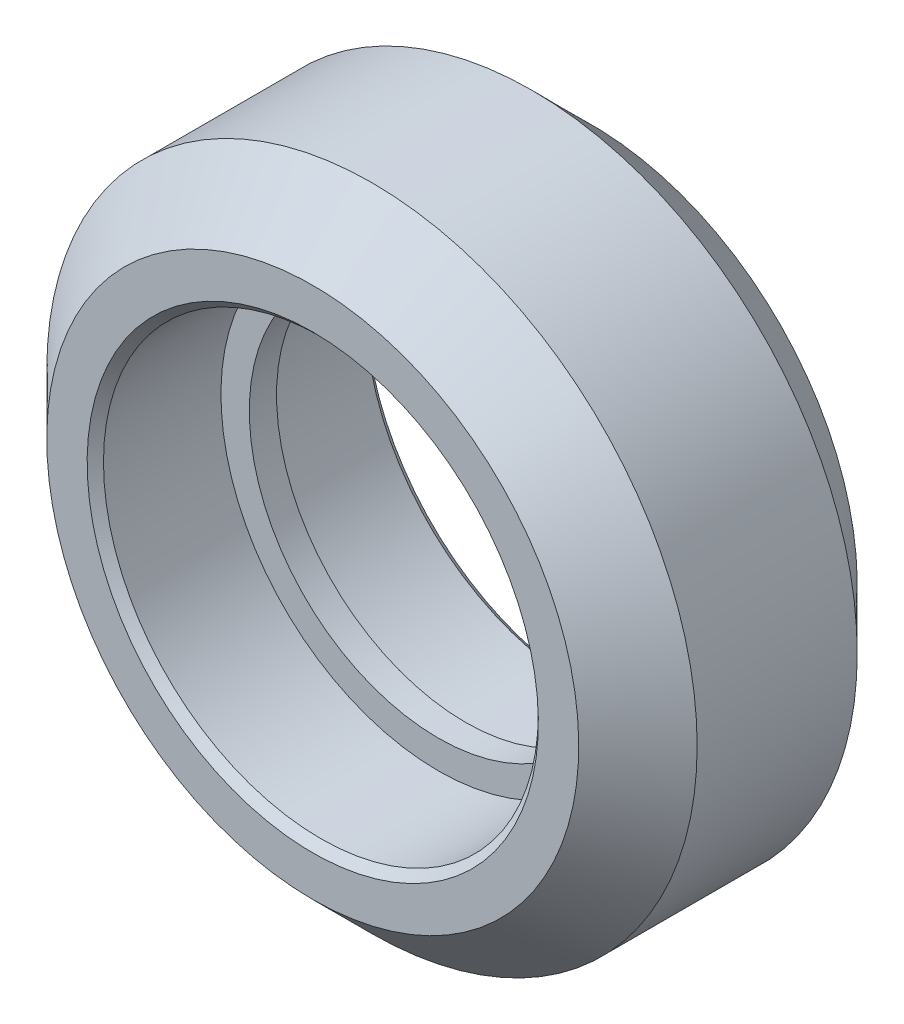
SolidWorks part; units mm, degrees
ref_plane "Front Plane" through (0, 0, 0) normal (0, 0, 1) x (1, 0, 0)
ref_plane "Top Plane" through (0, 0, 0) normal (0, 1, 0) x (1, 0, 0)
ref_plane "Right Plane" through (0, 0, 0) normal (1, 0, 0) x (0, 0, -1)
sketch "Sketch1" plane through (0, 0, 0) normal (1, 0, 0) x (0, 0, -1)
  line L0 (-5.115, 0) -> (5.115, 0) construction
  line L1 (-5.115, 11.945) -> (5.115, 11.945) construction
  line L2 (0, 11.945) -> (0, 0) construction
  line L3 (-5.115, 7.987) -> (5.115, 7.987) construction
  line L4 (-5.115, 9.77) -> (5.115, 9.77) construction
  line L5 (0, 11.945) -> (0, 15.716) construction
  line L6 (-0.5, 6.945) -> (0.5, 6.945) construction
  line L7 (-0.275, 9.375) -> (0.275, 9.375) construction
  line L8 (-2.7, 12.5215) -> (-2.7, 11.945) construction
  line L9 (-2.94, 11.945) -> (2.94, 11.945)
  line L10 (-2.94, 11.945) -> (-5.115, 9.77)
  line L11 (-5.115, 9.77) -> (-5.115, 7.987)
  line L12 (-5.115, 7.987) -> (-0.5, 7.987)
  line L13 (-0.5, 7.987) -> (-0.5, 6.945)
  line L14 (-0.5, 6.945) -> (0.5, 6.945)
  line L15 (-2.39, 11.945) -> (-0.275, 9.77) construction
  line L16 (-0.275, 9.77) -> (-0.275, 9.375) construction
  line L17 (-0.275, 9.375) -> (0.275, 9.375) construction
  line L18 (2.7, 12.5215) -> (2.7, 11.945) construction
  line L19 (0.275, 9.77) -> (0.275, 9.375) construction
  line L20 (2.39, 11.945) -> (0.275, 9.77) construction
  line L21 (0.5, 7.987) -> (0.5, 6.945)
  line L22 (5.115, 7.987) -> (0.5, 7.987)
  line L23 (5.115, 9.77) -> (5.115, 7.987)
  line L24 (2.94, 11.945) -> (5.115, 9.77)
  point P3 (0, 0)
  point P15 (0, 6.945)
  point P18 (0, 9.375)
  point P30 (0, 9.375)
  point P32 (0, 6.945)
  dimension "D1" = 10.23
  dimension "D2" = 11.945
  dimension "D3" = 7.987
  dimension "D4" = 9.77
  dimension "D5" = 6.945
  dimension "D6" = 1
  dimension "D7" = 9.375
  dimension "D8" = 0.55
  dimension "D9" = 2.7
  dimension "D10" = 0.55
  dimension "D11" = 45
ref_axis "Axis1" through (0, 0, 5.115) along (0, 0, -1)
revolve "Revolve1" add sketch "Sketch1" angle 360 about L0
chamfer "Chamfer1" distance 0.3 angle 45 2 edges at (0, -7.987, 5.115) (0, -7.987, -5.115)
